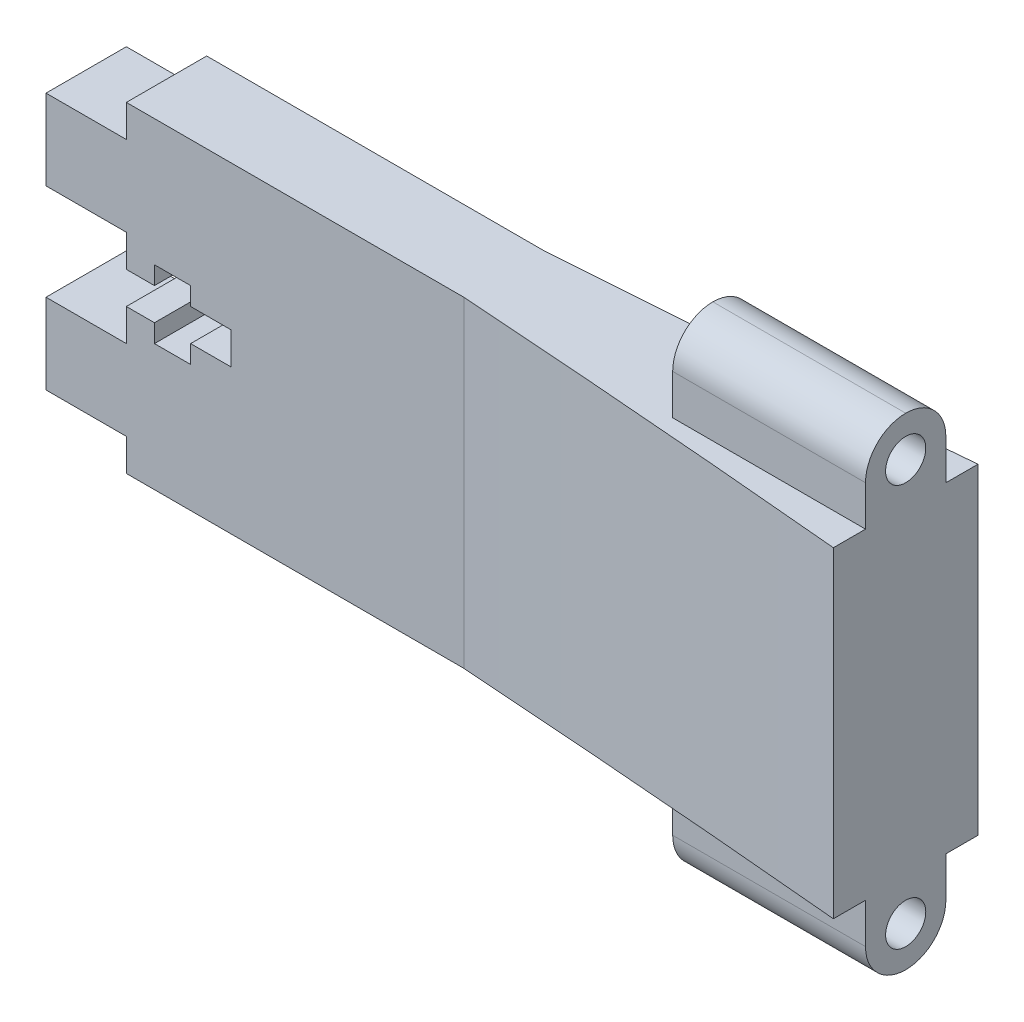
SolidWorks part; units mm, degrees
ref_plane "Front Plane" through (0, 0, 0) normal (0, 0, 1) x (1, 0, 0)
ref_plane "Top Plane" through (0, 0, 0) normal (0, 1, 0) x (1, 0, 0)
ref_plane "Right Plane" through (0, 0, 0) normal (1, 0, 0) x (0, 0, -1)
sketch "Sketch1" plane through (0, 0, 0) normal (0, 0, 1) x (1, 0, 0)
  line L5 (-38, 4.25) -> (-38, 2)
  line L6 (22, -20) -> (-46, -20)
  line L18 (0, 0) -> (0, -12.9172) construction
  line L42 (22, 20) -> (-46, 20)
  line L43 (-46, -20) -> (-46, -16)
  line L44 (46, -20) -> (-46, 20) construction
  line L45 (46, 20) -> (-46, -20) construction
  line L46 (-33, -2) -> (-38, -2)
  line L47 (-33, -2) -> (-33, 2)
  line L48 (-33, 2) -> (-38, 2)
  line L49 (-42.5, 4.25) -> (-42.5, 2)
  line L50 (-42.5, -4.25) -> (-38, -4.25)
  line L51 (-42.5, 4.25) -> (-38, 4.25)
  line L52 (-42.5, -2) -> (-46, -2)
  line L53 (-42.5, 2) -> (-46, 2)
  line L54 (-42.5, -2) -> (-42.5, -4.25)
  line L55 (-38, -2) -> (-38, -4.25)
  line L56 (0, 0) -> (-13.3376, 0) construction
  line L57 (-46, 2) -> (-46, 6)
  line L58 (-46, -16) -> (-56, -16)
  line L59 (-46, -6) -> (-56, -6)
  line L60 (-56, -16) -> (-56, -6)
  line L61 (-46, -6) -> (-46, -2)
  line L62 (-46, 16) -> (-56, 16)
  line L63 (-56, 16) -> (-56, 6)
  line L66 (-46, 6) -> (-56, 6)
  line L67 (-46, 16) -> (-46, 20)
  line L68 (46, -20) -> (46, -16)
  line L72 (46, -6) -> (46, -2)
  line L73 (46, -20) -> (46, -30)
  line L74 (46, -30) -> (22, -30)
  line L75 (22, -30) -> (22, -20)
  line L76 (46, 20) -> (46, 30)
  line L77 (46, 30) -> (22, 30)
  line L78 (22, 30) -> (22, 20)
  line L79 (46, 16) -> (46, 6)
  line L80 (46, -6) -> (46, -16)
  line L84 (46, 2) -> (46, 6)
  line L88 (46, 16) -> (46, 20)
  line L89 (46, 2) -> (46, -2)
  point P0 (0, 0)
  dimension "D15" = 24
  dimension "D1" = 40
  dimension "D2" = 92
  dimension "D3" = 33
  dimension "D4" = 4
  dimension "D5" = 6
  dimension "D6" = 5
  dimension "D7" = 4.5
  dimension "D8" = 4.25
  dimension "D9" = 4.25
  dimension "D10" = 4
  dimension "D11" = 4
  dimension "D12" = 10
  dimension "D13" = 24
  dimension "D14" = 10
  dimension "D16" = 10
  dimension "D17" = 0
  dimension "D18" = 0
extrude "Boss-Extrude1" add sketch "Sketch1" along normal mid plane 10 contours L42 L67 L62 L63 L66 L57 L53 L49 L51 L5 L48 L47 L46 L55 L50 L54 L52 L61 L59 L60 L58 L43 L6 region at (2.0965, 0, 0)
sketch "Sketch2" plane through (22, 0, 0) normal (-1, 0, 0) x (0, 0, 1)
  line L0 (5, -30) -> (-5, -30) construction
  line L1 (-5, -30) -> (-5, -20) construction
  circle A0 centre (0, -25) radius 2.5
  dimension "D2" = 5
  dimension "D1" = 5
  dimension "D3" = 5
extrude "Cut-Extrude1" cut sketch "Sketch2" against normal through all
sketch "Sketch3" plane through (22, 0, 0) normal (-1, 0, 0) x (0, 0, 1)
  line L0 (5, 30) -> (5, 20) construction
  line L1 (5, 30) -> (-5, 30) construction
  circle A0 centre (0, 25) radius 2.5
  dimension "D2" = 5
  dimension "D1" = 5
  dimension "D3" = 5
extrude "Cut-Extrude2" cut sketch "Sketch3" against normal through all
fillet "Fillet1" radius 5 4 edges at (34, -30, 5) (34, -30, -5) (34, 30, 5) (34, 30, -5)
sketch "Çizim2" plane through (0, 0, 0) normal (0, 1, 0) x (1, 0, 0)
  line L3 (46, 5) -> (-4, 5)
  line L4 (46, 5) -> (46, 9)
  spline S0 degree 2 poles (-4, 5) (21.0251, 6.6976) (46, 9) knots 0 0 0 1 1 1
  dimension "D1" = 5
  dimension "D2" = 50
  dimension "D3" = 4
  dimension "D4" = 46
  dimension "D5" = 2.86
  dimension "D6" = 12.8
extrude "Yükseklik-Ekstrüzyon1" add sketch "Çizim2" along normal mid plane 40
mirror "Mirror1" about plane through (0, 0, 0) normal (0, 0, 1) of "Yükseklik-Ekstrüzyon1"
